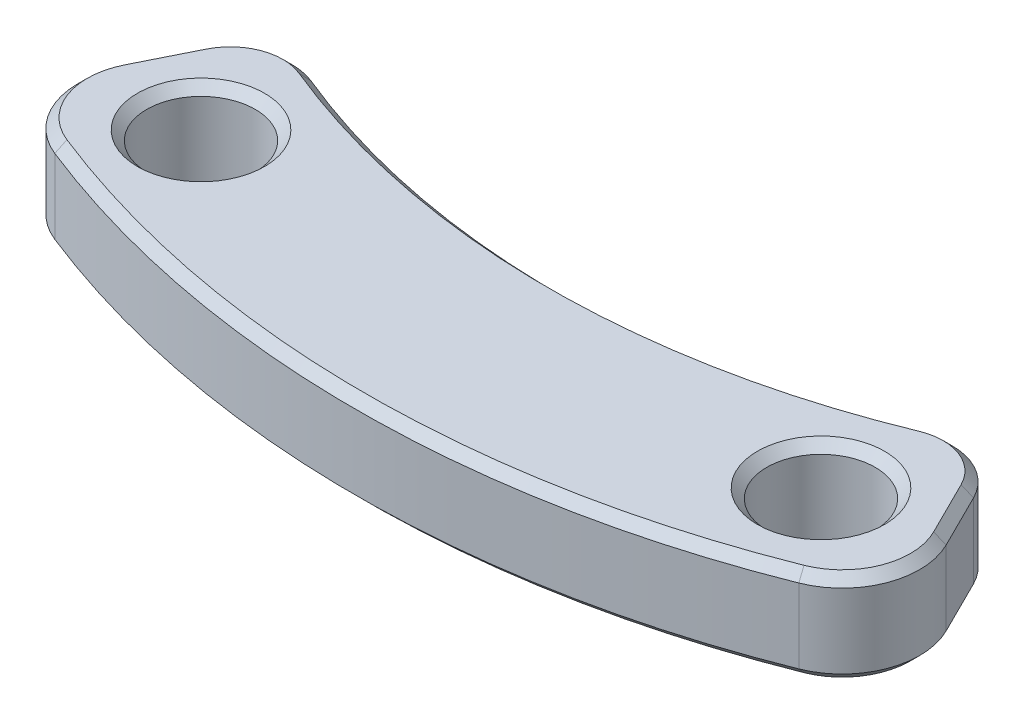
SolidWorks part; units mm, degrees
material "铸造合金钢"
ref_plane "前视基准面" through (0, 0, 0) normal (0, 0, 1) x (1, 0, 0)
ref_plane "上视基准面" through (0, 0, 0) normal (0, 1, 0) x (1, 0, 0)
ref_plane "右视基准面" through (0, 0, 0) normal (1, 0, 0) x (0, 0, -1)
other "Configuration Table"
sketch "草图1" plane through (0, 0, 0) normal (0, 1, 0) x (1, 0, 0)
  line L0 (-5.6188, 0.8044) -> (14.3812, 0.8044) construction
  line L2 (4.3812, 41.8964) -> (4.3812, -12.1119) construction
  line L3 (-8.0581, 3.2866) -> (-8.9343, 1.5253)
  line L5 (16.8205, 3.2866) -> (17.6966, 1.5253)
  line L6 (-7.1992, 5.0132) -> (4.3812, 28.2919) construction
  line L7 (4.3812, 28.2919) -> (15.9615, 5.0132) construction
  circle A0 centre (-5.6188, 0.8044) radius 1.75
  circle A1 centre (14.3812, 0.8044) radius 1.75
  arc A2 (14.2692, 4.2455) -> (-5.5068, 4.2455) centre (4.3812, 28.2919) cw
  arc A3 (16.3814, -1.9115) -> (-7.619, -1.9115) centre (4.3812, 28.2919) cw
  arc A4 (16.3814, -1.9115) -> (17.6966, 1.5253) centre (15.4583, 0.4118) ccw
  arc A5 (-7.619, -1.9115) -> (-8.9343, 1.5253) centre (-6.6959, 0.4118) cw
  arc A6 (14.2692, 4.2455) -> (16.8205, 3.2866) centre (15.0298, 2.3958) cw
  arc A7 (-5.5068, 4.2455) -> (-8.0581, 3.2866) centre (-6.2674, 2.3958) ccw
  dimension "D1" = 3.5
  dimension "D2" = 3.5
  dimension "D3" = 26
  dimension "D4" = 32.5
  dimension "D7" = 2.5
  dimension "D8" = 2
  dimension "D5" = 20
  dimension "D6" = 29.25
extrude "凸台-拉伸1" add sketch "草图1" along normal blind 3
chamfer "倒角1" distance 0.3 angle 45 20 edges at (14.3812, 0, 0.9456) (14.3812, 3, 0.9456) (-5.6188, 0, 0.9456) (-5.6188, 3, 0.9456) (4.3812, 0, -2.2919) (-6.9711, 0, -4.2679) (15.7335, 0, -4.2679) (-8.4962, 0, -2.4059) (17.2585, 0, -2.4059) (-9.0308, 0, 0.4817) (17.7932, 0, 0.4817) (4.3812, 0, 4.2081) (4.3812, 3, 4.2081) (17.7932, 3, 0.4817) (-9.0308, 3, 0.4817) (17.2585, 3, -2.4059) (-8.4962, 3, -2.4059) (15.7335, 3, -4.2679) (-6.9711, 3, -4.2679) (4.3812, 3, -2.2919)
